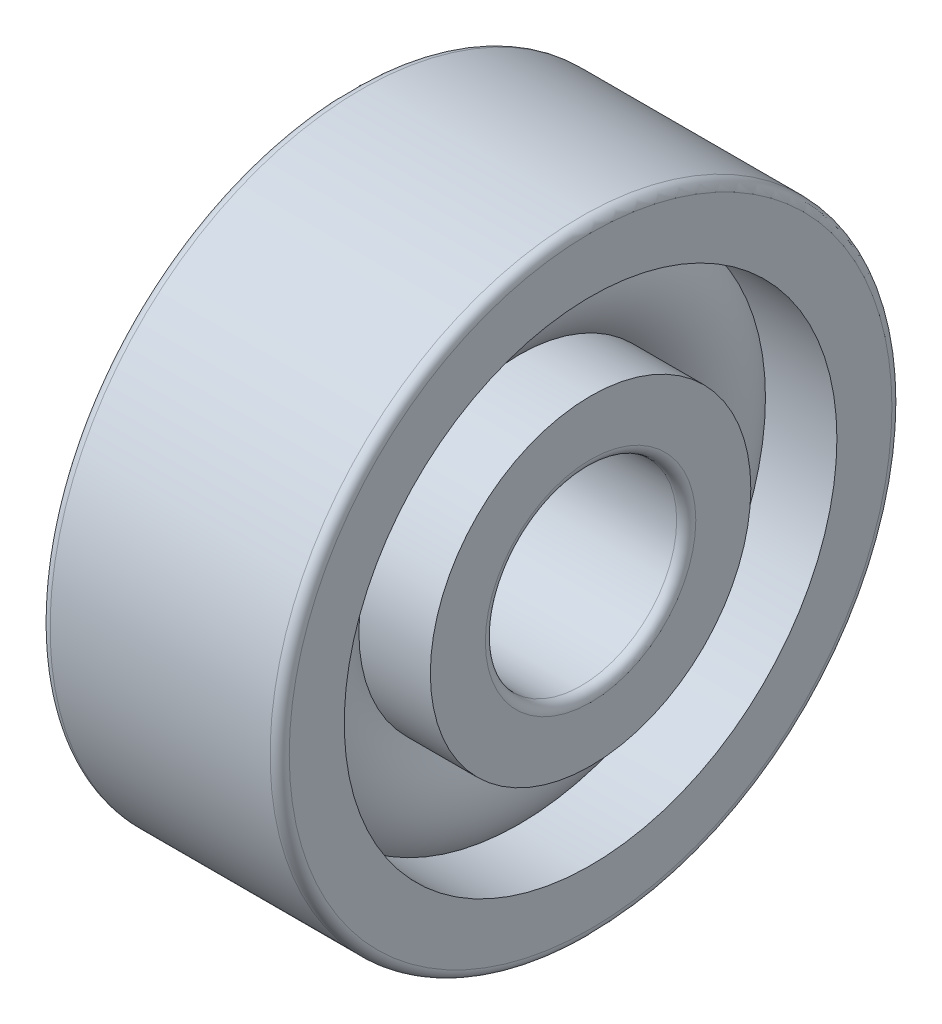
SolidWorks part; units mm, degrees
ref_plane "Plane1" through (0, 0, 0) normal (0, 0, 1) x (1, 0, 0)
ref_plane "Plane2" through (0, 0, 0) normal (0, 1, 0) x (1, 0, 0)
ref_plane "Plane3" through (0, 0, 0) normal (1, 0, 0) x (0, 0, -1)
sketch "Clipboard" plane through (0, 0, 0) normal (0, 0, 1) x (1, 0, 0)
  line L0 (-10, 0) -> (10, 0) construction
  line L1 (0, 0) -> (22.3471, -0.7804)
  line L2 (0, 0) -> (4.2474, 0.1483)
  line L3 (0, 0) -> (22.3471, -0.7804)
  line L4 (0, 0) -> (-22.3573, -0.3902)
sketch "CagSpiSke" plane through (0, 0, 0) normal (0, 0, 1) x (1, 0, 0)
  line L0 (0.135, 4.025) -> (0.135, 4.475)
  line L1 (0.135, 4.475) -> (-0.135, 4.475)
  line L2 (-0.135, 4.475) -> (-0.135, 4.025)
  line L3 (-0.135, 4.025) -> (0.135, 4.025)
  line L4 (-20.6375, 0) -> (20.6375, 0) construction
  line L5 (0, 0) -> (0, 23.7692) construction
revolve "CageSpine" add sketch "CagSpiSke" angle 0.001 about L4 reverse direction yes
ref_axis "Axis1" through (-50, 0, 0) along (1, 0, 0)
sketch "CagBalSke" plane through (0, 0, 0) normal (0, 0, 1) x (1, 0, 0)
  line L0 (-1.485, 4.25) -> (1.485, 4.25)
  line L1 (-1.905, 4.25) -> (1.905, 4.25) construction
  line L2 (-10, 0) -> (10, 0) construction
  line L3 (0, 0) -> (0, 24) construction
  arc A0 (1.485, 4.25) -> (-1.485, 4.25) centre (0, 4.25) cw
revolve "CageBall" [suppressed] add sketch "CagBalSke" angle 360 about L1 reverse direction yes
pattern_circular "CageBalls" [suppressed] count 2 every 180 about axis through (-50, 0, 0) along (1, 0, 0)
sketch "CagTrmODSke" plane through (0, 0, 0) normal (0, 0, 1) x (1, 0, 0)
  line L0 (1.486, 4.475) -> (1.486, 5.736)
  line L1 (1.486, 5.736) -> (-1.486, 5.736)
  line L2 (-1.486, 5.736) -> (-1.486, 4.475)
  line L3 (-1.486, 4.475) -> (1.486, 4.475)
  line L4 (-20.6375, 0) -> (20.6375, 0) construction
  line L5 (0, 0) -> (0, 25) construction
revolve "CageTrimOD" [suppressed] cut sketch "CagTrmODSke" angle 360 about L4 reverse direction yes
sketch "CagTrmIDSke" plane through (0, 0, 0) normal (0, 0, 1) x (1, 0, 0)
  line L0 (1.486, 2.766) -> (1.486, 4.025)
  line L1 (1.486, 4.025) -> (-1.486, 4.025)
  line L2 (-1.486, 4.025) -> (-1.486, 2.766)
  line L3 (-1.486, 2.766) -> (1.486, 2.766)
  line L4 (-20.6375, 0) -> (20.6375, 0) construction
  line L5 (0, 0) -> (0, 25) construction
revolve "CageTrimID" [suppressed] cut sketch "CagTrmIDSke" angle 360 about L4 reverse direction yes
sketch "BalSimSke" plane through (0, 0, 0) normal (0, 0, 1) x (1, 0, 0)
  line L0 (-10, 0) -> (10, 0) construction
  line L1 (-10, 4.25) -> (10, 4.25) construction
  line L2 (0, 0) -> (0, 23) construction
  circle A0 centre (0, 4.25) radius 1.35
revolve "BallsSimplified" add sketch "BalSimSke" angle 360 about L0
sketch "BalDetSke" plane through (0, 0, 0) normal (0, 0, 1) x (1, 0, 0)
  line L0 (-1.35, 4.25) -> (1.35, 4.25)
  line L1 (-1.905, 4.25) -> (1.905, 4.25) construction
  line L2 (0, 0) -> (0, 25) construction
  arc A0 (1.35, 4.25) -> (-1.35, 4.25) centre (0, 4.25) cw
revolve "BallDetailed" [suppressed] add sketch "BalDetSke" angle 360 about L1 reverse direction yes
sketch "InnRacSke" plane through (0, 0, 0) normal (0, 0, 1) x (1, 0, 0)
  line L0 (-0.9724, 3.35) -> (-2.5, 3.35)
  line L1 (-2.5, 3.35) -> (-2.5, 2.2)
  line L2 (-2.3, 2) -> (2.3, 2)
  line L3 (2.5, 2.2) -> (2.5, 3.35)
  line L4 (2.5, 3.35) -> (0.9724, 3.35)
  line L5 (-20.6375, 0) -> (20.6375, 0) construction
  line L6 (0, 0) -> (0, 30) construction
  arc A0 (-2.5, 2.2) -> (-2.3, 2) centre (-2.3, 2.2) ccw
  arc A1 (2.3, 2) -> (2.5, 2.2) centre (2.3, 2.2) ccw
  arc A2 (0.9724, 3.35) -> (-0.9724, 3.35) centre (0, 4.25) cw
revolve "InnerRace" add sketch "InnRacSke" angle 360 about L5 reverse direction yes
sketch "OutRacSke" plane through (0, 0, 0) normal (0, 0, 1) x (1, 0, 0)
  line L0 (-0.9724, 5.15) -> (-2.5, 5.15)
  line L1 (-2.5, 5.15) -> (-2.5, 6.3)
  line L2 (-2.3, 6.5) -> (2.3, 6.5)
  line L3 (2.5, 6.3) -> (2.5, 5.15)
  line L4 (2.5, 5.15) -> (0.9724, 5.15)
  line L5 (-20.6375, 0) -> (20.6375, 0) construction
  line L6 (0, 0) -> (0, 30) construction
  arc A0 (-2.5, 6.3) -> (-2.3, 6.5) centre (-2.3, 6.3) cw
  arc A1 (2.3, 6.5) -> (2.5, 6.3) centre (2.3, 6.3) cw
  arc A2 (0.9724, 5.15) -> (-0.9724, 5.15) centre (0, 4.25) ccw
revolve "OuterRace" add sketch "OutRacSke" angle 360 about L5 reverse direction yes
pattern_circular "BallsDetailed" [suppressed] count 2 every 180 about axis through (-50, 0, 0) along (1, 0, 0)
equation "\"BallCLRad@Clipboard\" = ( \"OD@OutRacSke\" + \"ID@InnRacSke\" ) / 4"
equation "\"BallCLRad@BalSimSke\" = \"BallCLRad@Clipboard\""
equation "\"BallCLRad@BalDetSke\" = \"BallCLRad@Clipboard\""
equation "\"BallCLRad@InnRacSke\" = \"BallCLRad@Clipboard\""
equation "\"BallCLRad@OutRacSke\" = \"BallCLRad@Clipboard\""
equation "\"Ball_diameter@InnRacSke\" = \"Ball_diameter@BalDetSke\" - 0.05"
equation "\"Ball_diameter@OutRacSke\" = \"Ball_diameter@BalDetSke\" - 0.05"
equation "\"Ball_diameter@BalSimSke\" = \"Ball_diameter@BalDetSke\""
equation "\"Width@OutRacSke\" = \"Width@InnRacSke\""
equation "\"Fillet_radius@OutRacSke\" = \"Fillet_radius@InnRacSke\""
equation "\"Max_count@Clipboard\" = int( 3.14159265 / atn(( \"Ball_diameter@BalDetSke\" / 2) / sqr( \"BallCLRad@Clipboard\"  *  \"BallCLRad@Clipboard\" - ( \"Ball_diameter@BalDetSke\" / 2) *  ( \"Ball_diameter@BalDetSke\" / 2))))"
equation "\"Max_count@Clipboard\" = ((sgn( \"Max_count@Clipboard\" - \"Count@Clipboard\" )-1)*( \"Max_count@Clipboard\" - \"Count@Clipboard\" ))/-2+ \"Count@Clipboard\""
equation "\"Count@BallsDetailed\" = int( \"Show_count@Clipboard\" ) "
equation "\"Count@BallsDetailed\" = ((sgn( \"Count@BallsDetailed\" - \"Max_count@Clipboard\" )-1)*( \"Count@BallsDetailed\" - \"Max_count@Clipboard\" ))/-2+ \"Max_count@Clipboard\""
equation "\"Count@BallsDetailed\" = ((sgn( \"Count@BallsDetailed\" - \"Min_count@Clipboard\" )+1)*( \"Count@BallsDetailed\" - \"Min_count@Clipboard\"))/2 +\"Min_count@Clipboard\""
equation "\"Angle@BallsDetailed\" = 360.0 / \"Max_count@Clipboard\""
equation "\"BallCLRad@CagBalSke\" = \"BallCLRad@Clipboard\""
equation "\"Count@CageBalls\" = \"Count@BallsDetailed\""
equation "\"Angle@CageBalls\" = \"Angle@BallsDetailed\""
equation "\"Angle@CageSpine\" =  \"Angle@CageBalls\" * ( \"Count@CageBalls\" -1 + int( \"Count@CageBalls\" / \"Max_count@Clipboard\" ) )  + 0.001 -  int( \"Count@CageBalls\" / \"Max_count@Clipboard\" ) * 0.001"
equation "\"Angle@CageSpine\" =  \"Angle@CageSpine\" * int( \"Min_count@Clipboard\" / 2) + int(1 / \"Min_count@Clipboard\")  * 0.001"
equation "\"CageWallOD@CagBalSke\" =  \"Ball_diameter@BalDetSke\" * 1.1"
equation "\"Thickness@CagSpiSke\" =  \"Ball_diameter@BalDetSke\" * 0.1"
equation "\"OD@CagTrmODSke\" = \"BallCLRad@Clipboard\" * 2 + \"CageWallOD@CagBalSke\" + 0.002"
equation "\"ID@CagTrmODSke\" = \"BallCLRad@Clipboard\" * 2 + \"Ball_diameter@BalDetSke\" / 6"
equation "\"OD@CagTrmIDSke\" = \"BallCLRad@Clipboard\" * 2 - \"Ball_diameter@BalDetSke\" / 6"
equation "\"ID@CagTrmIDSke\" = \"BallCLRad@Clipboard\" * 2 - \"CageWallOD@CagBalSke\" + 0.002"
equation "\"OD@CagSpiSke\" = \"ID@CagTrmODSke\""
equation "\"ID@CagSpiSke\" = \"OD@CagTrmIDSke\""
equation "\"Width@CagTrmODSke\" = \"CageWallOD@CagBalSke\" + 0.002"
equation "\"Width@CagTrmIDSke\" = \"CageWallOD@CagBalSke\" + 0.002"
